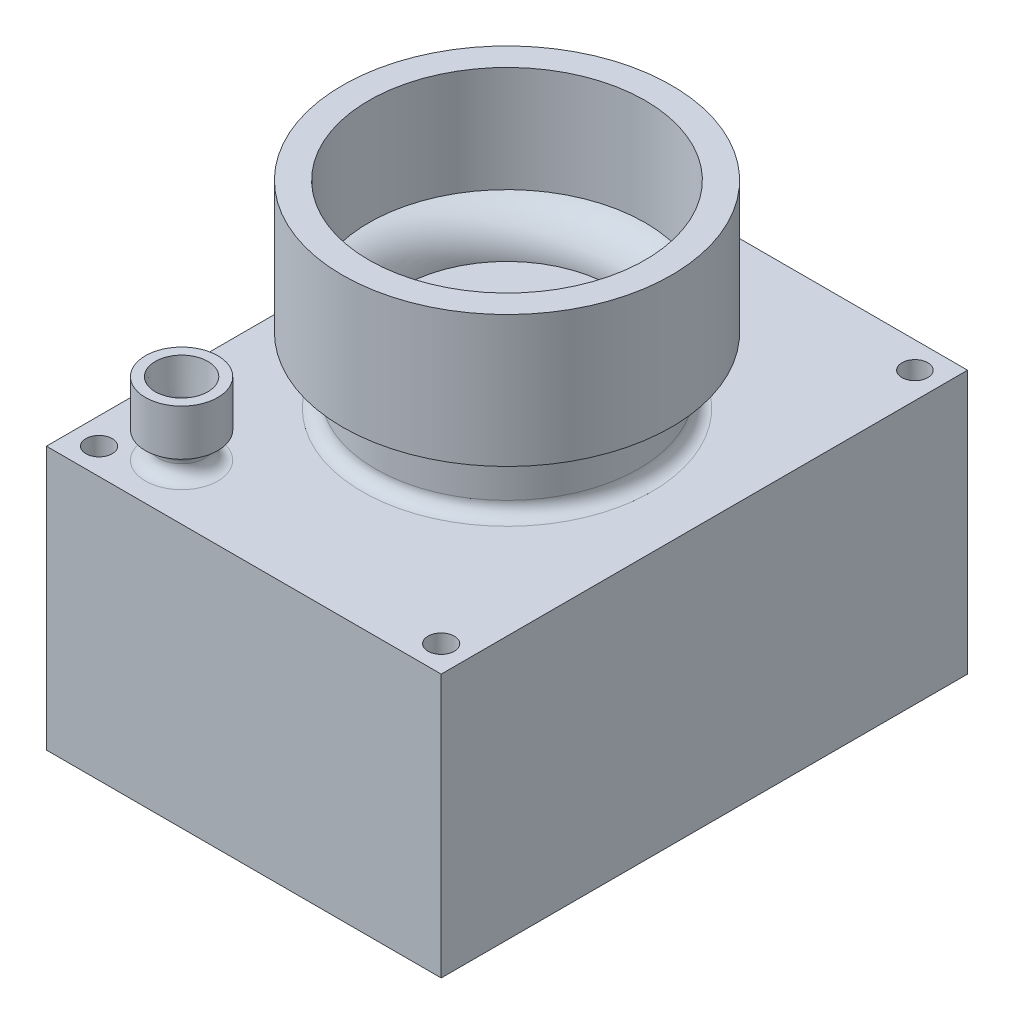
SolidWorks part; units mm, degrees
material "ABS"
ref_plane "Front Plane" through (0, 0, 0) normal (0, 0, 1) x (1, 0, 0)
ref_plane "Top Plane" through (0, 0, 0) normal (0, 1, 0) x (1, 0, 0)
ref_plane "Right Plane" through (0, 0, 0) normal (1, 0, 0) x (0, 0, -1)
sketch "Sketch1" plane through (0, 0, 0) normal (0, 1, 0) x (1, 0, 0)
  line L1 (-38.1, -50.8) -> (38.1, -50.8)
  line L2 (-38.1, -50.8) -> (-38.1, 50.8)
  line L3 (-38.1, 50.8) -> (38.1, 50.8)
  line L4 (38.1, -50.8) -> (38.1, 50.8)
  line L5 (-38.1, -50.8) -> (38.1, 50.8) construction
  line L6 (-38.1, 50.8) -> (38.1, -50.8) construction
  point P0 (0, 0)
  dimension "D1" = 76.2
  dimension "D2" = 101.6
extrude "Boss-Extrude1" add sketch "Sketch1" along normal blind 50.8
sketch "Sketch2" plane through (0, 50.8, 0) normal (0, 1, 0) x (1, 0, 0)
  circle A0 centre (0, 0) radius 25.4
  dimension "D1" = 50.8
extrude "Boss-Extrude2" add sketch "Sketch2" along normal blind 12.7
sketch "Sketch3" plane through (0, 63.5, 0) normal (0, 1, 0) x (1, 0, 0)
  circle A0 centre (0, 0) radius 31.75
  dimension "D1" = 63.5
extrude "Boss-Extrude3" add sketch "Sketch3" along normal blind 25.4
fillet "Fillet1" radius 2.54 1 edges at (0, 50.8, -25.4)
fillet "Fillet2" radius 2.54 1 edges at (0, 63.5, 25.4)
shell "Shell1" thickness 5.08 removed face at (0, 88.9, 31.75)
surface "Surface-Fill1"
sketch "Sketch4" plane through (0, 50.8, 0) normal (0, 1, 0) x (1, 0, 0)
  line L0 (38.1, 50.8) -> (-38.1, 50.8) construction
  line L1 (-38.1, 50.8) -> (-38.1, -50.8) construction
  line L2 (38.1, -50.8) -> (38.1, 50.8) construction
  line L3 (-38.1, -50.8) -> (38.1, -50.8) construction
  circle A0 centre (-33.02, 45.72) radius 2.54
  circle A1 centre (33.0128, 45.72) radius 2.4981
  circle A2 centre (-33.02, -45.72) radius 2.54
  circle A3 centre (33.0128, -45.72) radius 2.54
  dimension "D3" = 4.9962
  dimension "D4" = 5.08
  dimension "D7" = 5.08
  dimension "D10" = 5.08
  dimension "D1" = 5.08
  dimension "D2" = 5.08
  dimension "D5" = 5.08
  dimension "D6" = 5.0872
  dimension "D8" = 5.08
  dimension "D9" = 5.08
  dimension "D11" = 5.0872
  dimension "D12" = 5.08
extrude "Cut-Extrude1" cut sketch "Sketch4" against normal through all
sketch "Sketch5" plane through (0, 50.8, 0) normal (0, 1, 0) x (1, 0, 0)
  circle A0 centre (-22.7139, -40.0934) radius 4.445
  dimension "D1" = 8.89
extrude "Boss-Extrude4" add sketch "Sketch5" along normal blind 5.08
sketch "Sketch6" plane through (0, 55.88, 0) normal (0, 1, 0) x (1, 0, 0)
  circle A0 centre (-22.7139, -40.0934) radius 6.985
  dimension "D1" = 13.97
extrude "Boss-Extrude5" add sketch "Sketch6" along normal blind 8.89
sketch "Sketch7" plane through (0, 64.77, 0) normal (0, 1, 0) x (1, 0, 0)
  circle A0 centre (-22.7139, -40.0934) radius 5.08
  dimension "D1" = 10.16
extrude "Cut-Extrude2" cut sketch "Sketch7" against normal blind 8.89 draft 5
fillet "Fillet3" radius 2.54 1 edges at (-22.7139, 50.8, 35.6484)
fillet "Fillet4" radius 2.54 1 edges at (-22.7139, 55.88, 44.5384)
fillet "Fillet5" radius 2.54 1 edges at (-22.7139, 55.88, 44.3957)
